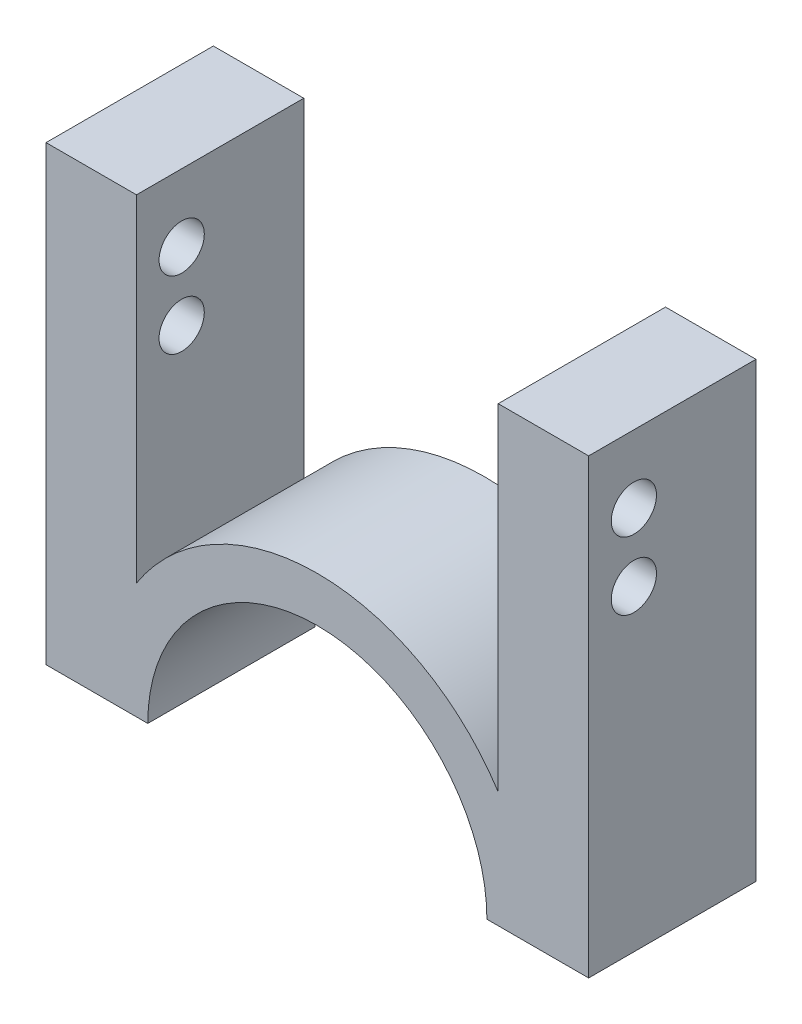
SolidWorks part; units mm, degrees
ref_plane "Płaszczyzna przednia" through (0, 0, 0) normal (0, 0, 1) x (1, 0, 0)
ref_plane "Płaszczyzna górna" through (0, 0, 0) normal (0, 1, 0) x (1, 0, 0)
ref_plane "Płaszczyzna prawa" through (0, 0, 0) normal (1, 0, 0) x (0, 0, -1)
sketch "Szkic1" plane through (0, 0, 0) normal (0, 0, 1) x (1, 0, 0)
  line L0 (37.5, 0) -> (47.5, 0)
  line L1 (-37.5, 0) -> (-47.5, 0)
  line L2 (-47.5, 0) -> (-60, 0)
  line L3 (47.5, 0) -> (60, 0)
  line L4 (-60, 0) -> (-60, 20)
  line L5 (60, 0) -> (60, 20)
  line L8 (-60, 20) -> (-60, 100)
  line L9 (60, 20) -> (60, 100)
  line L10 (60, 100) -> (40, 100)
  line L11 (-60, 100) -> (-40, 100)
  line L12 (-40, 100) -> (-40, 25.6174)
  line L13 (40, 100) -> (40, 25.6174)
  arc A0 (37.5, 0) -> (-37.5, 0) centre (0, 0) ccw
  arc A1 (40, 25.6174) -> (-40, 25.6174) centre (0, 0) ccw
  dimension "D1" = 75
  dimension "D2" = 95
  dimension "D3" = 95
  dimension "D4" = 12.5
  dimension "D5" = 12.5
  dimension "D6" = 20
  dimension "D7" = 20
  dimension "D8" = 22.5
  dimension "D9" = 22.5
  dimension "D10" = 80
  dimension "D11" = 80
  dimension "D12" = 20
  dimension "D13" = 20
extrude "Dodanie-wyciągnięcie1" add sketch "Szkic1" along normal blind 37
sketch "Szkic2" plane through (60, 0, 0) normal (1, 0, 0) x (0, 0, -1)
  line L0 (-37, 100) -> (0, 100) construction
  line L2 (-37, 0) -> (-37, 100) construction
  circle A0 centre (-27, 85) radius 5
  circle A1 centre (-27, 70) radius 5
  dimension "D2" = 10
  dimension "D3" = 10
  dimension "D4" = 30
  dimension "D1" = 15
  dimension "D5" = 10
  dimension "D6" = 10
extrude "Wytnij-wyciągnięcie1" cut sketch "Szkic2" against normal blind 127
